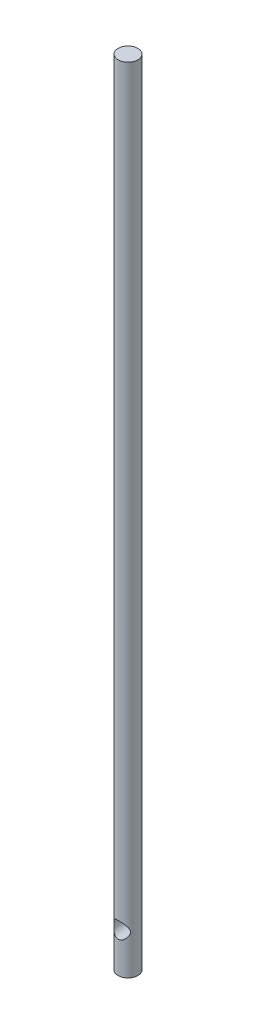
SolidWorks part; units mm, degrees
ref_plane "Front Plane" through (0, 0, 0) normal (0, 0, 1) x (1, 0, 0)
ref_plane "Top Plane" through (0, 0, 0) normal (0, 1, 0) x (1, 0, 0)
ref_plane "Right Plane" through (0, 0, 0) normal (1, 0, 0) x (0, 0, -1)
sketch "Sketch1" plane through (0, 0, 0) normal (0, 1, 0) x (1, 0, 0)
  circle A0 centre (0, 0) radius 3.175
  dimension "D1" = 6.35
extrude "Boss-Extrude1" add sketch "Sketch1" along normal blind 254
sketch "Sketch2" plane through (0, 0, 0) normal (0, 0, 1) x (1, 0, 0)
  line L0 (-3.175, 0) -> (3.175, 0) construction
  circle A0 centre (0, 12.7) radius 2.6035
  dimension "D2" = 5.207
  dimension "D1" = 12.7
extrude "Cut-Extrude1" cut sketch "Sketch2" against normal blind 254 and the other way blind 254 contours A0
